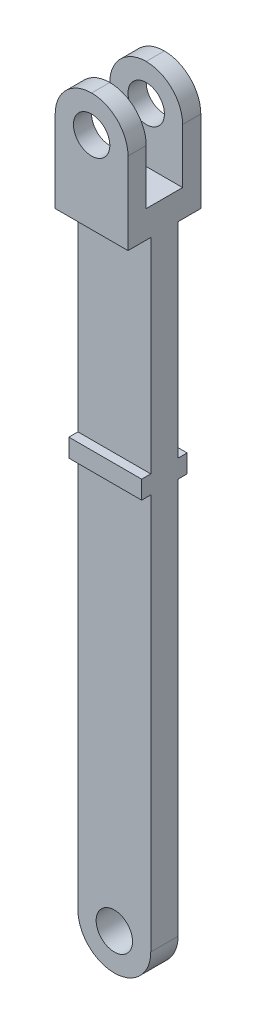
SolidWorks part; units mm, degrees
ref_plane "Alzado" through (0, 0, 0) normal (0, 0, 1) x (1, 0, 0)
ref_plane "Planta" through (0, 0, 0) normal (0, 1, 0) x (1, 0, 0)
ref_plane "Vista lateral" through (0, 0, 0) normal (1, 0, 0) x (0, 0, -1)
sketch "Croquis1" plane through (0, 0, 0) normal (0, 0, 1) x (1, 0, 0)
  line L0 (0, 42.5) -> (0, 32.5) construction
  line L1 (-4, -42.5) -> (4, -42.5)
  line L2 (-4, -42.5) -> (-4, 32.5)
  line L4 (4, -42.5) -> (4, 32.5)
  line L5 (-4, -42.5) -> (3.0588, 32.5) construction
  line L6 (-3.0588, 32.5) -> (4, -42.5) construction
  line L7 (4, 32.5) -> (-4, 32.5)
  point P0 (0, 0)
  point P11 (0, 32.5)
  dimension "D3" = 10
extrude "Saliente-Extruir1" add sketch "Croquis1" along normal blind 3
sketch "Croquis2" plane through (0, 0, 3) normal (0, 0, 1) x (1, 0, 0)
  line L0 (0, -42.5) -> (0, -38.5) construction
  line L1 (-4, -42.5) -> (4, -42.5) construction
  line L2 (0, 0) -> (2.8858, 0) construction
  circle A0 centre (0, -38.5) radius 2
  dimension "D2" = 4
  dimension "D1" = 4
extrude "Cortar-Extruir1" cut sketch "Croquis2" against normal through all contours A0
sketch "Croquis3" plane through (0, 0, 3) normal (0, 0, 1) x (1, 0, 0)
  line L0 (0, 0) -> (0, 6) construction
  line L1 (4, -42.5) -> (4, 32.5) construction
  line L2 (-4, 5) -> (4, 5)
  line L3 (-4, 5) -> (-4, 7)
  line L4 (-4, 7) -> (4, 7)
  line L5 (4, 5) -> (4, 7)
  line L6 (-4, 5) -> (4, 7) construction
  line L7 (-4, 7) -> (4, 5) construction
  dimension "D1" = 6
  dimension "D2" = 2
extrude "Saliente-Extruir2" add sketch "Croquis3" along normal blind 1
ref_plane "Plano1" through (0, 0, 1.5) normal (0, 0, 1) x (1, 0, 0)
mirror "Simetría1" about plane through (0, 0, 1.5) normal (0, 0, 1) of "Saliente-Extruir2"
sketch "Croquis4" plane through (0, 0, 0) normal (0, 0, -1) x (-1, 0, 0)
  line L2 (4, 32.5) -> (4, 7) construction
  line L3 (-4, 29.5) -> (4, 29.5)
  line L4 (-4, 29.5) -> (-4, 32.5)
  line L5 (-4, 32.5) -> (4, 32.5)
  line L6 (4, 29.5) -> (4, 32.5)
  line L7 (-4, 29.5) -> (4, 32.5) construction
  line L8 (-4, 32.5) -> (4, 29.5) construction
  dimension "D2" = 3
extrude "Saliente-Extruir3" add sketch "Croquis4" along normal blind 2.5
sketch "Croquis5" plane through (0, 32.5, 0) normal (0, 1, 0) x (1, 0, 0)
  line L0 (4, 2.5) -> (4, -3) construction
  line L1 (-4, 2.5) -> (4, 2.5)
  line L2 (-4, 2.5) -> (-4, 0.5)
  line L3 (-4, 0.5) -> (4, 0.5)
  line L4 (4, 2.5) -> (4, 0.5)
  dimension "D1" = 2
extrude "Saliente-Extruir4" add sketch "Croquis5" along normal blind 10
sketch "Croquis7" plane through (0, 0, -2.5) normal (0, 0, -1) x (-1, 0, 0)
  line L0 (0, 42.5) -> (0, 38.5) construction
  line L1 (-4, 42.5) -> (4, 42.5) construction
  circle A0 centre (0, 38.5) radius 2
  dimension "D2" = 4
  dimension "D1" = 4
extrude "Cortar-Extruir3" cut sketch "Croquis7" against normal blind 18.5 contours A0
fillet "Redondeo2" radius 4 4 edges at (4, 42.5, -1.5) (-4, 42.5, -1.5) (-4, -42.5, 1.5) (4, -42.5, 1.5)
mirror "Simetría3" about plane through (0, 0, 1.5) normal (0, 0, 1) of "Cortar-Extruir3", "Saliente-Extruir3", "Saliente-Extruir4"
fillet "Redondeo5" radius 4 2 edges at (-4, 42.5, 4.5) (4, 42.5, 4.5)
